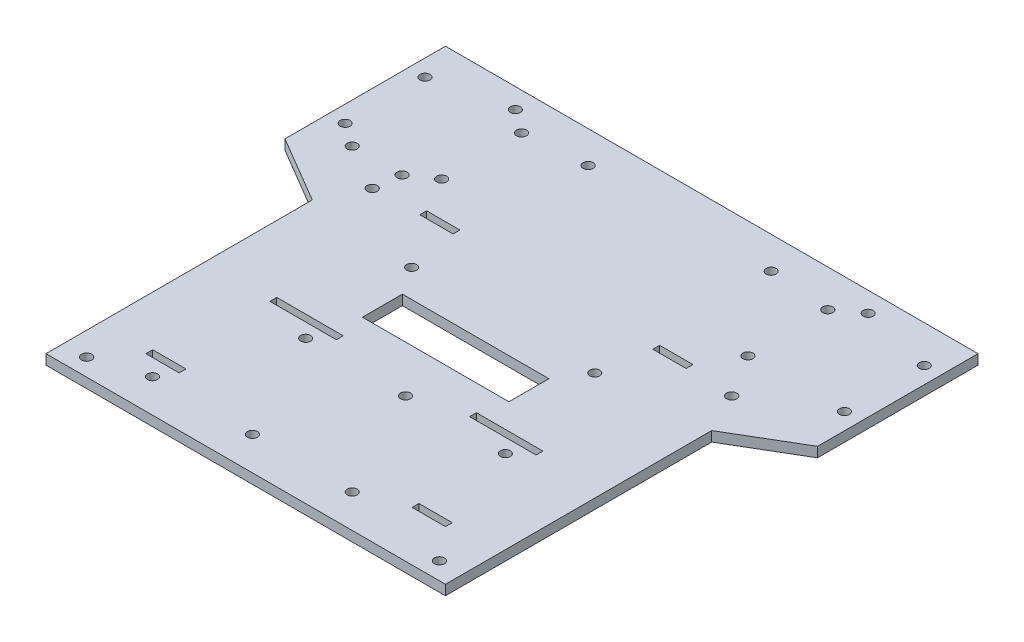
SolidWorks part; units mm, degrees
ref_plane "Front Plane" through (0, 0, 0) normal (0, 0, 1) x (1, 0, 0)
ref_plane "Top Plane" through (0, 0, 0) normal (0, 1, 0) x (1, 0, 0)
ref_plane "Right Plane" through (0, 0, 0) normal (1, 0, 0) x (0, 0, -1)
sketch "Sketch1" plane through (0, 0, 0) normal (0, 1, 0) x (1, 0, 0)
  line L0 (-60, 10) -> (-80, 21.7918)
  line L1 (60, -70) -> (-60, -70)
  line L2 (60, -70) -> (60, 70)
  line L3 (60, 70) -> (-60, 70)
  line L4 (-60, -70) -> (-60, 70)
  line L5 (60, -70) -> (-60, 70) construction
  line L6 (60, 70) -> (-60, -70) construction
  line L7 (-80, 21.7918) -> (-80, 70)
  line L8 (-80, 70) -> (-60, 70)
  line L9 (0, 0) -> (0, 70) construction
  line L10 (60, 10) -> (80, 21.7918)
  line L11 (80, 70) -> (60, 70)
  line L12 (80, 21.7918) -> (80, 70)
  point P0 (0, 0)
  dimension "D1" = 140
  dimension "D2" = 120
  dimension "D3" = 20
  dimension "D4" = 30.523
  dimension "D5" = 60
extrude "Boss-Extrude1" add sketch "Sketch1" along normal blind 3 contours L4 L1 L2 L3 | L8 L7 L0 L4 | L10 L12 L11 L2 region at (0, 0, 0) region at (-69.6368, 0, -42.8409) region at (69.6368, 0, -42.8409)
sketch "Sketch2" plane through (0, 3, 0) normal (0, 1, 0) x (1, 0, 0)
  line L2 (0, 0) -> (0, -70) construction
  line L3 (60, -70) -> (-60, -70) construction
  circle A0 centre (-38, -60) radius 1.5
  circle A1 centre (-25, -27) radius 1.5
  circle A2 centre (5, -27) radius 1.5
  circle A3 centre (-8, -60) radius 1.5
  circle A4 centre (35, -27) radius 1.5
  circle A5 centre (22, -60) radius 1.5
  dimension "D1" = 3
  dimension "D2" = 38
  dimension "D3" = 10
  dimension "D4" = 3
  dimension "D6" = 33
  dimension "D5" = 13
  dimension "D7" = 3
extrude "Cut-Extrude1" cut sketch "Sketch2" against normal through all
sketch "Sketch3" plane through (0, 3, 0) normal (0, 1, 0) x (1, 0, 0)
  line L0 (-0.0296, 57.8856) -> (-0.0296, -0.1144) construction
  line L1 (-30.0296, 33.8856) -> (29.9704, 33.8856) construction
  line L4 (-80, 21.7918) -> (-80, 70) construction
  line L6 (-80, 21.7918) -> (-80, 70) construction
  line L7 (80, 70) -> (-80, 70) construction
  line L8 (-60, 10) -> (-60, 70) construction
  line L9 (60, 10) -> (60, 70) construction
  circle A0 centre (-27.5296, 60.3856) radius 1.5
  circle A1 centre (-27.5296, 7.3856) radius 1.5
  circle A2 centre (27.4704, 7.3856) radius 1.5
  circle A3 centre (27.4704, 60.3856) radius 1.5
  point P16 (-80, 45.8959)
  dimension "D1" = 52.4704
  dimension "D2" = 36.1144
  dimension "D3" = 3
  dimension "D4" = 79.9704
  dimension "D5" = 26.5
extrude "Cut-Extrude3" cut sketch "Sketch3<2>" against normal through all
sketch "Sketch3<2>" plane through (0, 3, 0) normal (0, 1, 0) x (1, 0, 0) same geometry as "Sketch3"
extrude "Cut-Extrude2" cut sketch "Sketch3" against normal through all rebuild error yes
sketch "Sketch4" plane through (0, 3, 0) normal (0, 1, 0) x (1, 0, 0)
  line L0 (-60.5, 58.8639) -> (-60.5, 32.8639) construction
  line L1 (-80, 21.7918) -> (-80, 70) construction
  line L2 (80, 70) -> (-80, 70) construction
  line L3 (0, 0) -> (0, 70) construction
  circle A0 centre (-75, 34.8639) radius 1.5
  circle A1 centre (-75, 58.8639) radius 1.5
  circle A2 centre (-46, 34.8639) radius 1.5
  circle A3 centre (-46, 58.8639) radius 1.5
  circle A4 centre (46, 58.8639) radius 1.5
  circle A5 centre (46, 34.8639) radius 1.5
  circle A6 centre (75, 34.8639) radius 1.5
  circle A7 centre (75, 58.8639) radius 1.5
  dimension "D1" = 3
  dimension "D2" = 3
  dimension "D5" = 5
  dimension "D6" = 11.1361
  dimension "D7" = 5
  dimension "D3" = 24
  dimension "D4" = 14.5
extrude "Cut-Extrude4" cut sketch "Sketch4" against normal through all
sketch "Sketch5" plane through (0, 3, 0) normal (0, 1, 0) x (1, 0, 0)
  line L0 (80, 70) -> (-80, 70) construction
  line L1 (-80, 21.7918) -> (-80, 70) construction
  circle A0 centre (-68, 30) radius 1.5
  circle A1 centre (-53, 30) radius 1.5
  dimension "D1" = 3
  dimension "D2" = 3
  dimension "D3" = 40
  dimension "D4" = 40
  dimension "D6" = 12
  dimension "D5" = 15
extrude "Cut-Extrude5" cut sketch "Sketch5" against normal blind 3
sketch "Sketch6" plane through (0, 3, 0) normal (0, 1, 0) x (1, 0, 0)
  line L0 (60, -70) -> (-60, -70) construction
  line L1 (-45, -52.95) -> (-35, -52.95)
  line L2 (-45, -52.95) -> (-45, -55)
  line L3 (-45, -55) -> (-35, -55)
  line L4 (-35, -52.95) -> (-35, -55)
  line L5 (-45, -52.95) -> (-35, -55) construction
  line L6 (-45, -55) -> (-35, -52.95) construction
  line L7 (-60, -70) -> (-60, 10) construction
  line L8 (0, 0) -> (0, -70) construction
  line L9 (35, -52.95) -> (35, -55)
  line L10 (45, -55) -> (35, -55)
  line L11 (45, -52.95) -> (45, -55)
  line L12 (45, -52.95) -> (35, -52.95)
  line L13 (20, -22.75) -> (20, -20.7)
  line L14 (-20, -22.75) -> (-40, -22.75)
  line L15 (-20, -22.75) -> (-20, -20.7)
  line L16 (-20, -20.7) -> (-40, -20.7)
  line L17 (-40, -22.75) -> (-40, -20.7)
  line L18 (-20, -22.75) -> (-40, -20.7) construction
  line L19 (-20, -20.7) -> (-40, -22.75) construction
  line L20 (20, -22.75) -> (40, -22.75)
  line L21 (40, -22.75) -> (40, -20.7)
  line L22 (20, -20.7) -> (40, -20.7)
  line L23 (-60, -30) -> (60, -30) construction
  line L24 (60, -70) -> (60, 10) construction
  line L25 (-30, -21.725) -> (60, -21.725) construction
  line L26 (30, 24.35) -> (30, 22.3)
  line L27 (-40, 24.35) -> (-30, 24.35)
  line L28 (-40, 24.35) -> (-40, 22.3)
  line L29 (-40, 22.3) -> (-30, 22.3)
  line L30 (-30, 24.35) -> (-30, 22.3)
  line L31 (-40, 24.35) -> (-30, 22.3) construction
  line L32 (-40, 22.3) -> (-30, 24.35) construction
  line L33 (40, 24.35) -> (40, 22.3)
  line L34 (40, 24.35) -> (30, 24.35)
  line L35 (40, 22.3) -> (30, 22.3)
  circle A0 centre (-53, -64.8) radius 1.525
  circle A1 centre (53, -64.8) radius 1.525
  point P0 (-40, -53.975)
  point P16 (-30, -21.725)
  point P31 (-35, 23.325)
  dimension "D9" = 7
  dimension "D11" = 3.05
  dimension "D1" = 2.05
  dimension "D2" = 15
  dimension "D3" = 15
  dimension "D4" = 10
  dimension "D5" = 2.05
  dimension "D6" = 30.2
  dimension "D7" = 20
  dimension "D8" = 20
  dimension "D10" = 5.2
  dimension "D12" = 10
  dimension "D13" = 5
  dimension "D14" = 2.05
  dimension "D15" = 43
extrude "Cut-Extrude7" cut sketch "Sketch6" against normal through all
sketch "Sketch9" plane through (0, 3, 0) normal (0, 1, 0) x (1, 0, 0)
  line L0 (80, 70) -> (-80, 70) construction
  line L1 (-80, 21.7918) -> (-80, 70) construction
  line L2 (0, 0) -> (0, 70) construction
  circle A0 centre (-54, 22) radius 1.525
  circle A2 centre (54, 22) radius 1.525
  dimension "D1" = 3.05
  dimension "D2" = 48
  dimension "D3" = 26
extrude "Cut-Extrude8" cut sketch "Sketch9" against normal blind 3
sketch "Sketch10" plane through (0, 3, 0) normal (0, 1, 0) x (1, 0, 0)
  line L0 (60, -70) -> (60, 10) construction
  line L1 (22.0465, -12.9751) -> (-21.9535, -12.9751)
  line L2 (22.0465, -12.9751) -> (22.0465, -0.9751)
  line L3 (22.0465, -0.9751) -> (-21.9535, -0.9751)
  line L4 (-21.9535, -12.9751) -> (-21.9535, -0.9751)
  line L5 (22.0465, -12.9751) -> (-21.9535, -0.9751) construction
  line L6 (22.0465, -0.9751) -> (-21.9535, -12.9751) construction
  line L7 (80, 70) -> (-80, 70) construction
  point P0 (0.0465, -6.9751)
  dimension "D1" = 12
  dimension "D2" = 44
  dimension "D3" = 37.9535
  dimension "D4" = 70.9751
extrude "Cut-Extrude9" cut sketch "Sketch10" against normal blind 5
sketch "Sketch11" plane through (0, 3, 0) normal (0, 1, 0) x (1, 0, 0)
  line L0 (80, 70) -> (-80, 70) construction
  line L1 (0, 0) -> (0, 70) construction
  line L2 (-80, 21.7918) -> (-80, 70) construction
  circle A0 centre (-53, 64) radius 1.5
  circle A1 centre (53, 64) radius 1.5
  dimension "D1" = 3
  dimension "D3" = 27
  dimension "D2" = 6
extrude "Cut-Extrude10" cut sketch "Sketch11" against normal blind 5
